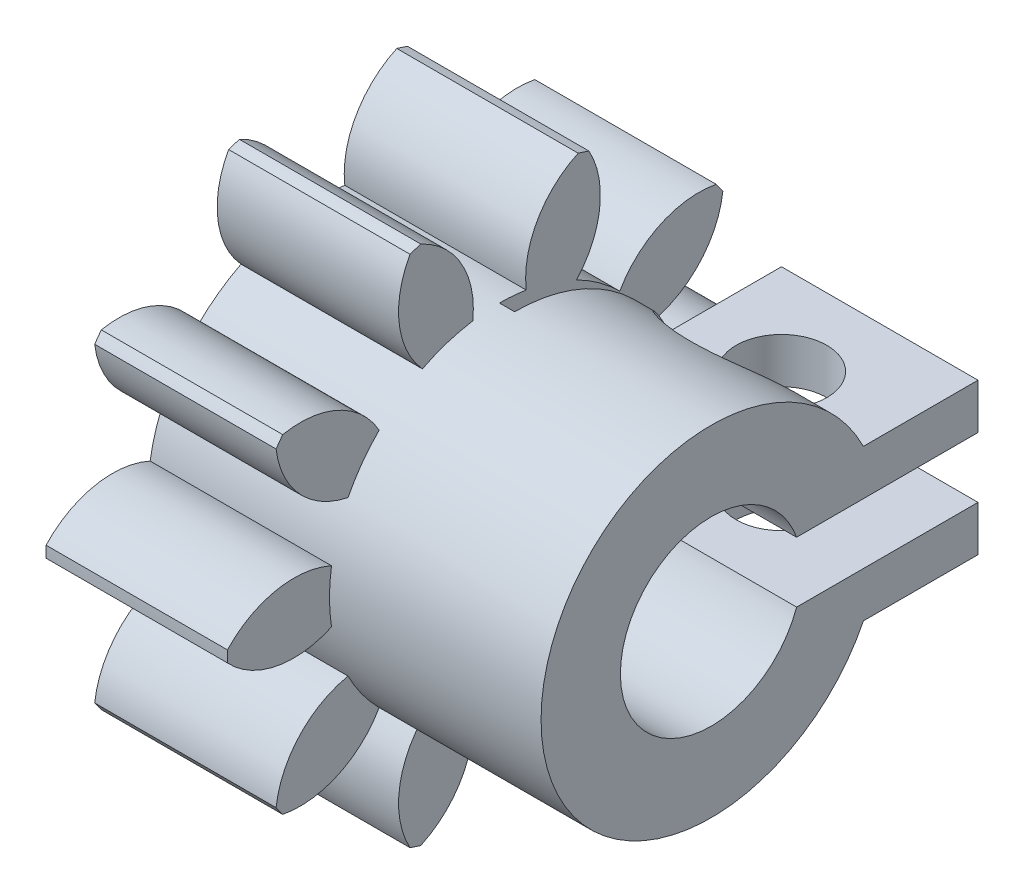
SolidWorks part; units mm, degrees
ref_plane "Plane1" through (0, 0, 0) normal (0, 0, 1) x (1, 0, 0)
ref_plane "Plane2" through (0, 0, 0) normal (0, 1, 0) x (1, 0, 0)
ref_plane "Plane3" through (0, 0, 0) normal (1, 0, 0) x (0, 0, -1)
sketch "HoldingSke" plane through (0, 0, 0) normal (0, 1, 0) x (1, 0, 0)
  line L0 (0, 0) -> (0.6565, -0.1158)
  line L1 (-15, 0) -> (100, 0) construction
  line L2 (0, 0) -> (-2.1039, 2.3779)
  line L3 (0, 0) -> (-11.863, 4.5341)
  line L4 (0, 0) -> (8.5048, 1.4996)
  line L5 (0, 0) -> (-46.8476, -17.4728)
  line L6 (0, 0) -> (-4.9738, -3.3558)
  line L7 (-2.1039, 2.3779) -> (8.6586, 51.2059)
  line L8 (-76.2, 54.61) -> (-75.2, 54.61)
  line L9 (-71.009, 38.7566) -> (-53.1078, 45.2721)
  line L10 (-76.2, 71.12) -> (104.1128, 71.12)
  line L11 (0, 0) -> (-6, 0)
  line L12 (-76.2, 101.6) -> (-76.147, 101.6)
  line L13 (24.9733, 27.94) -> (52.9518, 28.4284)
  line L14 (24.9733, 27.94) -> (24.9743, 27.94)
  line L15 (24.9733, 27.94) -> (100.4006, 29.5858)
  line L16 (-63.627, -1.5) -> (-12.827, -1.5)
  circle A0 centre (0, 0) radius 3
  circle A1 centre (0, 0) radius 5.624
  circle A2 centre (0, 0) radius 37.5
  circle A3 centre (0, 0) radius 3
  dimension "Num_teeth" = 10
  dimension "Pitch_radius" = 180.3128
  dimension "Width" = 6
  dimension "Thickness" = 6
sketch "BasProSke" plane through (0, 0, 0) normal (0, 1, 0) x (1, 0, 0)
  line L0 (-10, 0) -> (60, 0) construction
  line L1 (0, 0) -> (0, 9)
  line L2 (0, 0) -> (6, 0)
  line L3 (6, 0) -> (6, 9)
  line L4 (6, 9) -> (0, 9)
  dimension "Thickness" = 6
  dimension "Diameter" = 18
revolve "Base-Revolve" add sketch "BasProSke" angle 360 about L0
sketch "TooCutSke" plane through (0, 0, 0) normal (1, 0, 0) x (0, 0, -1)
  line L1 (0, 0) -> (0, 107) construction
  line L2 (0, 0) -> (-1.2658, 7.3924) construction
  line L3 (0, 0) -> (-4.5869, 14.117) construction
  line L4 (-1.2658, 7.3924) -> (-2.2934, 7.0585) construction
  arc A0 (0.8839, 5.5541) -> (-0.8839, 5.5541) centre (0, 0) ccw
  arc A1 (2.6378, 8.6313) -> (-2.6378, 8.6313) centre (0, 0) ccw
  circle A2 centre (0, 0) radius 7.5 construction
  circle A3 centre (0, 0) radius 7.0477 construction
  arc A4 (-0.8839, 5.5541) -> (-2.6378, 8.6313) centre (-3.8646, 5.8936) ccw
  arc A5 (2.6378, 8.6313) -> (0.8839, 5.5541) centre (3.8646, 5.8936) ccw
extrude "ToothCut" cut sketch "TooCutSke" along normal through all
fillet "Breaks" [suppressed] radius 0.03 tangent propagation no
fillet "RootFillets" [suppressed] radius 0.376
pattern_circular "TeethCuts" count 10 every 36 about axis through (-10, 0, 0) along (1, 0, 0) of "ToothCut", "RootFillets", "Breaks"
sketch "HubNeaOneSke" plane through (0, 0, 0) normal (-1, 0, 0) x (0, 0, 1)
  circle A0 centre (0, 0) radius 5.624
  dimension "Diameter" = 11.248
extrude "HubNearOne" [suppressed] add sketch "HubNeaOneSke" along normal blind 44.0001
sketch "HubNeaBotSke" plane through (0, 0, 0) normal (-1, 0, 0) x (0, 0, 1)
  circle A0 centre (0, 0) radius 5.624
  dimension "Diameter" = 11.248
extrude "HubNearBoth" [suppressed] add sketch "HubNeaBotSke" along normal blind 22
ref_plane "FarPln" through (6, 0, 0) normal (1, 0, 0) x (0, 0, -1)
sketch "HubFarSke" plane through (6, 0, 0) normal (1, 0, 0) x (0, 0, -1)
  circle A0 centre (0, 0) radius 5.624
  dimension "Diameter" = 11.248
extrude "HubFar" [suppressed] add sketch "HubFarSke" along normal blind 22
sketch "BorSke" plane through (0, 0, 0) normal (1, 0, 0) x (0, 0, -1)
  circle A0 centre (0, 0) radius 3
  dimension "Diameter" = 6
extrude "Bore" cut sketch "BorSke" along normal mid plane 100.0001
sketch "KeySke" plane through (0, 0, 0) normal (1, 0, 0) x (0, 0, -1)
  line L0 (-1, 0) -> (-1, 4)
  line L1 (-1, 4) -> (1, 4)
  line L2 (1, 4) -> (1, 0)
  line L3 (0, 0) -> (0, 34) construction
  line L4 (-1, 0) -> (1, 0)
  dimension "Width" = 2
extrude "Keyway" [suppressed] cut sketch "KeySke" along normal mid plane 100.0001
pattern_circular "Keyway2" [suppressed] count 2 every 90 about axis through (-10, 0, 0) along (1, 0, 0) reverse direction yes
sketch "Sketch1" plane through (6, 0, 0) normal (1, 0, 0) x (0, 0, -1)
  circle A0 centre (0, 0) radius 5.624
  circle M2 centre (0, 0) radius 3
  arc M4 (5.5554, 0.8757) -> (5.0091, 2.5569) centre (0, 0) ccw
  arc M8 (3.9797, 3.9738) -> (2.5496, 5.0129) centre (0, 0) ccw
  arc M12 (0.8839, 5.5541) -> (-0.8839, 5.5541) centre (0, 0) ccw
  arc M16 (-2.5496, 5.0129) -> (-3.9797, 3.9738) centre (0, 0) ccw
  arc M20 (-5.0091, 2.5569) -> (-5.5554, 0.8757) centre (0, 0) ccw
  arc M24 (-5.5554, -0.8757) -> (-5.0091, -2.5569) centre (0, 0) ccw
  arc M28 (-3.9797, -3.9738) -> (-2.5496, -5.0129) centre (0, 0) ccw
  arc M32 (-0.8839, -5.5541) -> (0.8839, -5.5541) centre (0, 0) ccw
  arc M36 (2.5496, -5.0129) -> (3.9797, -3.9738) centre (0, 0) ccw
  arc M40 (5.0091, -2.5569) -> (5.5554, -0.8757) centre (0, 0) ccw
extrude "Boss-Extrude1" add sketch "Sketch1" along normal blind 7 contours A0 M4 M8 M12 M16 M20 M24 M28 M32 M36 M40 M2 region at (6, -0.4268, -5.4482)
sketch "Sketch3" plane through (13, 0, 0) normal (1, 0, 0) x (0, 0, -1)
  line L1 (1.2388, -1) -> (7.2538, -1)
  line L2 (1.2388, -1) -> (1.2388, 1)
  line L3 (1.2388, 1) -> (7.2538, 1)
  line L4 (7.2538, -1) -> (7.2538, 1)
  line L5 (1.2388, -1) -> (7.2538, 1) construction
  line L6 (1.2388, 1) -> (7.2538, -1) construction
  point P0 (4.2463, 0)
  point P5 (4.0592, 0)
  point P6 (1.9606, 0)
  point P7 (4.2864, 0)
  point P9 (0, 0)
  point P10 (4.2463, 0)
  dimension "D1" = 2
extrude "Cut-Extrude1" cut sketch "Sketch3" against normal up to surface (7 mm away) up to face at (6, 4.3202, -5.9463)
sketch "Sketch4" plane through (0, -1, 0) normal (0, 1, 0) x (1, 0, 0)
  line L1 (6, 2.8284) -> (13, 2.8284)
  line L2 (6, 2.8284) -> (6, 8.8284)
  line L3 (6, 8.8284) -> (13, 8.8284)
  line L4 (13, 2.8284) -> (13, 8.8284)
  point P5 (13, 2.8284)
  dimension "D1" = 6
extrude "Boss-Extrude2" add sketch "Sketch4" against normal blind 1.5 contours L4 L3 L2 L1
mirror "Mirror1" about plane through (0, 0, 0) normal (0, 1, 0) of "Boss-Extrude2"
sketch "Sketch5" plane through (0, -1, 0) normal (0, 1, 0) x (1, 0, 0)
  line L0 (13, 8.8284) -> (6, 2.8284) construction
  line L1 (13, 2.8284) -> (6, 8.8284) construction
  circle A0 centre (9.5, 5.8284) radius 1.5
  dimension "D1" = 3
extrude "Cut-Extrude2" cut sketch "Sketch5" against normal through all and the other way through all contours A0
sketch "Sketch6" plane through (0, 2.5, 0) normal (0, 1, 0) x (1, 0, 0)
  circle A0 centre (9.5, 5.8284) radius 3
  dimension "D1" = 6
extrude "Cut-Extrude3" cut sketch "Sketch6" along normal through all contours A0
mirror "Mirror2" about plane through (0, 0, 0) normal (0, 1, 0) of "Cut-Extrude3"
sketch "Sketch7" plane through (0, 0, 0) normal (0, 0, 1) x (1, 0, 0)
  line L0 (6, -3.9738) -> (6, -2.5569) construction
  line L1 (6.5, 6.5304) -> (6, 6.5304)
  line L2 (6.5, 6.5304) -> (6.5, -7.6094)
  line L3 (6.5, -7.6094) -> (6, -7.6094)
  line L4 (6, 6.5304) -> (6, -7.6094)
  dimension "D1" = 0.5
extrude "Cut-Extrude4" cut sketch "Sketch7" against normal through all
equation "' \"Module@HoldingSke\" = 6.35"
equation "' \"Num_teeth@HoldingSke\" = 12"
equation "' \"Ap@HoldingSke\" =  20"
equation "' \"Ap@HoldingSke\" = 20"
equation "' \"Width@HoldingSke\" = 0.5 * 25.4"
equation "' \"Hub_dia@HoldingSke\"= 1 * 25.4"
equation "' \"Hub_dia@HoldingSke\" = 1 * 25.4"
equation "' \"Overall_len@HoldingSke\" = 1.0 * 25.4"
equation "' \"Bore@HoldingSke\" = 0.75 * 25.4"
equation "' \"T_dim@HoldingSke\" = 0.1 * 25.4"
equation "' \"Width@KeySke\" = 0.25 * 25.4"
equation "' \"Show_teeth@HoldingSke\" = 13"
equation "' \"Backlash@HoldingSke\" = 0.009 * 25.4"
equation "' \"Addendum_fac@HoldingSke\" = 1.0"
equation "' \"Dedendum_fac@HoldingSke\" = 1.25"
equation "' \"Dedendum_add@HoldingSke\" = 0.00005 * 25.4"
equation "' \"Clearance_fac@HoldingSke\" = 0.25"
equation "\"Pitch@HoldingSke\" = 1 / \"Module@HoldingSke\""
equation "\"Overcut_dia@TooCutSke\" = (\"Num_teeth@HoldingSke\" + 2 * \"Addendum_fac@HoldingSke\") / \"Pitch@HoldingSke\" + 0.002 * 25.4"
equation "\"Pitch_dia@TooCutSke\" = \"Num_teeth@HoldingSke\" / \"Pitch@HoldingSke\""
equation "\"Base_dia@TooCutSke\" = \"Num_teeth@HoldingSke\" / \"Pitch@HoldingSke\" * cos((\"Ap@HoldingSke\"  * 3.14159265 / 180))"
equation "\"Root_dia@TooCutSke\" = (\"Num_teeth@HoldingSke\" + 2) / \"Pitch@HoldingSke\" - 2 * (\"Addendum_fac@HoldingSke\" + \"Dedendum_fac@HoldingSke\") / \"Pitch@HoldingSke\" - \"Dedendum_add@HoldingSke\" * 2"
equation "\"Half_ang@TooCutSke\" = 180 / \"Num_teeth@HoldingSke\""
equation "\"Half_CT@TooCutSke\" = \"Num_teeth@HoldingSke\" / \"Pitch@HoldingSke\" * sin((3.14159265 / 2 / \"Num_teeth@HoldingSke\")) / 2 - 7 * \"Backlash@HoldingSke\" / 4"
equation "\"Flank_rad@TooCutSke\" = \"Num_teeth@HoldingSke\" / \"Pitch@HoldingSke\" / 5"
equation "\"Radius@RootFillets\" = \"Clearance_fac@HoldingSke\" / \"Pitch@HoldingSke\" + \"Dedendum_add@HoldingSke\""
equation "\"Break_rad@Breaks\" = 0.02 / \"Pitch@HoldingSke\""
equation "\"Thickness@HoldingSke\" = \"Width@HoldingSke\""
equation "\"OAL@HoldingSke\" = \"Thickness@HoldingSke\""
equation "\"MHD@HoldingSke\" = (\"Num_teeth@HoldingSke\" + 2) / \"Pitch@HoldingSke\" - 2 * (\"Addendum_fac@HoldingSke\" + \"Dedendum_fac@HoldingSke\")  / \"Pitch@HoldingSke\" - \"Dedendum_add@HoldingSke\" * 2"
equation "\"MBD@HoldingSke\" = (\"Num_teeth@HoldingSke\" + 2) / \"Pitch@HoldingSke\" - 2 * (\"Addendum_fac@HoldingSke\" + \"Dedendum_fac@HoldingSke\")  / \"Pitch@HoldingSke\" - \"Dedendum_add@HoldingSke\" * 2 - 0.002 * 25.4"
equation "\"MHD@HoldingSke\" = ((sgn( \"MHD@HoldingSke\" - \"Hub_dia@HoldingSke\" )-1)*( \"MHD@HoldingSke\" - \"Hub_dia@HoldingSke\" ))/-2+ \"Hub_dia@HoldingSke\""
equation "\"MBD@HoldingSke\" = ((sgn( \"MBD@HoldingSke\" - \"Bore@HoldingSke\" )-1)*( \"MBD@HoldingSke\" - \"Bore@HoldingSke\" ))/-2+ \"Bore@HoldingSke\""
equation "\"OAL@HoldingSke\" = ((sgn( \"OAL@HoldingSke\" - \"Overall_len@HoldingSke\" )+1)*( \"OAL@HoldingSke\" - \"Overall_len@HoldingSke\" ))/2 + \"Overall_len@HoldingSke\" + 0.000002 * 25.4"
equation "\"Num_teeth@TeethCuts\" = int( \"Show_teeth@HoldingSke\" ) + 1"
equation "\"Num_teeth@TeethCuts\" = ((sgn( \"Num_teeth@TeethCuts\" - \"Num_teeth@HoldingSke\" )-1)*( \"Num_teeth@TeethCuts\" - \"Num_teeth@HoldingSke\" ))/-2+ \"Num_teeth@HoldingSke\""
equation "\"Num_teeth@TeethCuts\" = ((sgn( \"Num_teeth@TeethCuts\" - 2.0)+1)*( \"Num_teeth@TeethCuts\" - 2.0))/2 +2.0"
equation "\"Angle@TeethCuts\" = 360.0 / \"Num_teeth@HoldingSke\""
equation "\"Diameter@BasProSke\" = (\"Num_teeth@HoldingSke\" + 2 * \"Addendum_fac@HoldingSke\") / \"Pitch@HoldingSke\""
equation "\"Thickness@BasProSke\"  = \"Thickness@HoldingSke\""
equation "' \"Fillet_rad@BasProSke\" =  \"Thickness@HoldingSke\" * 0.05"
equation "' \"Fillet_rad@BasProSke\" = \"Thickness@HoldingSke\" * 0.05"
equation "\"MHD@HoldingSke\" = ((sgn( \"MHD@HoldingSke\" - \"Root_dia@TooCutSke\" )-1)*( \"MHD@HoldingSke\" - \"Root_dia@TooCutSke\" ))/-2+ \"Root_dia@TooCutSke\""
equation "\"Diameter@HubNeaOneSke\" = \"MHD@HoldingSke\""
equation "\"Length@HubNearOne\" = \"OAL@HoldingSke\" - \"Thickness@BasProSke\""
equation "\"Diameter@HubNeaBotSke\" = \"MHD@HoldingSke\""
equation "\"Length@HubNearBoth\" = ( \"OAL@HoldingSke\" - \"Thickness@BasProSke\" ) / 2.0"
equation "\"Thickness@FarPln\" = \"Thickness@BasProSke\""
equation "\"Diameter@HubFarSke\" = \"MHD@HoldingSke\""
equation "\"Length@HubFar\" = ( \"OAL@HoldingSke\" - \"Thickness@BasProSke\" ) / 2.0"
equation "\"Diameter@BorSke\" = \"MBD@HoldingSke\""
equation "\"D1@Bore\" = \"OAL@HoldingSke\" * 2.0"
equation "\"D1@Keyway\" = \"OAL@HoldingSke\" * 2.0"
equation "\"Offset@KeySke\" = \"T_dim@HoldingSke\" + \"MBD@HoldingSke\" / 2.0"
